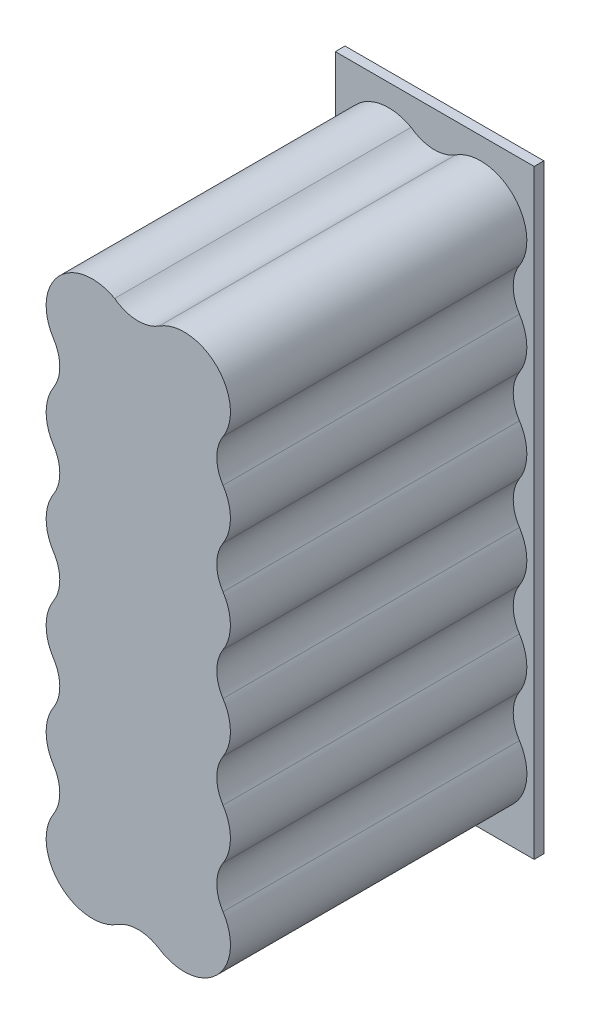
SolidWorks part; units mm, degrees
ref_plane "前视基准面" through (0, 0, 0) normal (0, 0, 1) x (1, 0, 0)
ref_plane "上视基准面" through (0, 0, 0) normal (0, 1, 0) x (1, 0, 0)
ref_plane "右视基准面" through (0, 0, 0) normal (1, 0, 0) x (0, 0, -1)
sketch "Sketch1" plane through (0, 0, 0) normal (0, 0, 1) x (1, 0, 0)
  arc A1 (18.1174, 26.9644) -> (4.982, 40.0999) centre (10.1391, 32.1216) ccw
  arc A2 (-16.7564, 18.2802) -> (-16.8424, 8.0985) centre (-8.779, 13.1216) ccw
  arc A4 (-16.7564, -0.7198) -> (-16.8424, -10.9015) centre (-8.779, -5.8784) ccw
  arc A6 (-16.7564, -19.7198) -> (-16.8424, -29.9015) centre (-8.779, -24.8784) ccw
  arc A8 (-16.7564, -38.7198) -> (-16.8424, -48.9015) centre (-8.779, -43.8784) ccw
  arc A10 (-16.7564, -57.7198) -> (-3.6533, -70.877) centre (-8.779, -62.8784) ccw
  arc A12 (-4.1864, 40.4377) -> (4.982, 40.0999) centre (0.6391, 46.8185) ccw
  arc A13 (-16.8424, 27.0985) -> (-16.7564, 18.2802) centre (-23.4742, 22.6242) cw
  arc A14 (-16.8424, 8.0985) -> (-16.7564, -0.7198) centre (-23.4742, 3.6242) cw
  arc A15 (18.1174, 26.9644) -> (18.1174, 18.2787) centre (24.836, 22.6216) ccw
  arc A16 (18.1174, 7.9644) -> (18.1174, -0.7213) centre (24.836, 3.6216) ccw
  arc A17 (-16.8424, -10.9015) -> (-16.7564, -19.7198) centre (-23.4742, -15.3758) cw
  arc A18 (18.1174, -11.0356) -> (18.1174, -19.7213) centre (24.836, -15.3784) ccw
  arc A19 (-16.8424, -29.9015) -> (-16.7564, -38.7198) centre (-23.4742, -34.3758) cw
  arc A20 (18.1174, -30.0356) -> (18.1174, -38.7213) centre (24.836, -34.3784) ccw
  arc A21 (-16.8424, -48.9015) -> (-16.7564, -57.7198) centre (-23.4742, -53.3758) cw
  arc A22 (18.1174, -49.0356) -> (18.1174, -57.7213) centre (24.836, -53.3784) ccw
  arc A23 (-3.6533, -70.877) -> (4.9932, -70.8858) centre (0.6631, -77.6127) cw
  arc A38 (18.1174, 7.9644) -> (18.1174, 18.2787) centre (10.1391, 13.1216) ccw
  arc A39 (18.1174, -11.0356) -> (18.1174, -0.7213) centre (10.1391, -5.8784) ccw
  arc A40 (18.1174, -30.0356) -> (18.1174, -19.7213) centre (10.1391, -24.8784) ccw
  arc A41 (18.1174, -49.0356) -> (18.1174, -38.7213) centre (10.1391, -43.8784) ccw
  arc A44 (4.9932, -70.8858) -> (18.1174, -57.7213) centre (10.1391, -62.8917) ccw
  arc A45 (-4.1864, 40.4377) -> (-16.8424, 27.0985) centre (-8.779, 32.1216) ccw
  point P18 (0, -38)
  dimension "D1" = 19
  dimension "D3" = 8
  dimension "D4" = 5
extrude "Extrude1" add sketch "Sketch1" along normal blind 61 contours A1 | A2 | A4 | A6 | A8 | A10 region at (0.6817, -15.3882, 0)
sketch "Sketch2" plane through (0, 0, 0) normal (0, 0, -1) x (-1, 0, 0)
  line L1 (-21.1391, 46.1216) -> (19.779, 46.1216)
  line L2 (-21.1391, 46.1216) -> (-21.1391, -77.3784)
  line L3 (-21.1391, -77.3784) -> (19.779, -77.3784)
  line L4 (19.779, 46.1216) -> (19.779, -77.3784)
  circle A0 centre (-10.1391, 32.1216) radius 9.5 construction
  circle A2 centre (8.779, -62.8784) radius 9.5 construction
  arc A3 (16.8424, 27.0985) -> (4.1864, 40.4377) centre (8.779, 32.1216) ccw construction
  dimension "D1" = 11
  dimension "D3" = 11
  dimension "D2" = 14
  dimension "D4" = 14.5
extrude "Extrude6" add sketch "Sketch2" along normal blind 2
